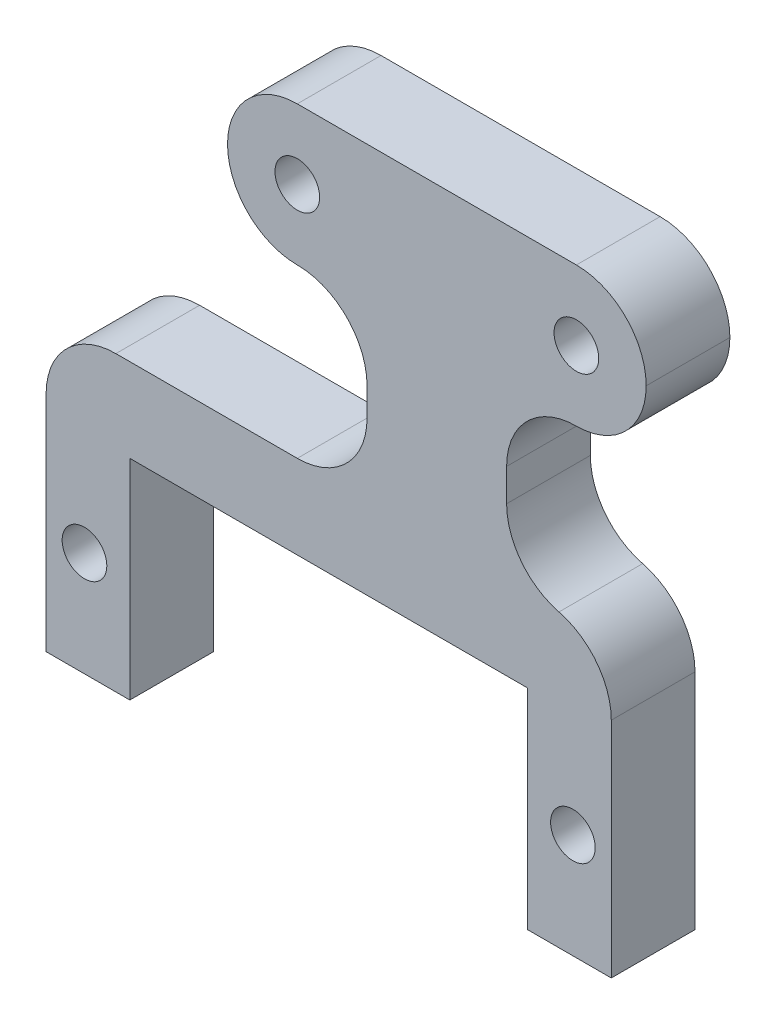
SolidWorks part; units mm, degrees
ref_plane "Plan de face" through (0, 0, 0) normal (0, 0, 1) x (1, 0, 0)
ref_plane "Plan de dessus" through (0, 0, 0) normal (0, 1, 0) x (1, 0, 0)
ref_plane "Plan de droite" through (0, 0, 0) normal (1, 0, 0) x (0, 0, -1)
sketch "Esquisse1" plane through (0, 0, 0) normal (0, 0, 1) x (1, 0, 0)
  line L0 (12.75, 18) -> (22.75, 18)
  line L1 (-14.25, 0) -> (14.25, 0)
  line L2 (-20.25, 0) -> (-20.25, 6)
  line L3 (-20.25, 6) -> (2.75, 6)
  line L4 (20.25, -0.6948) -> (20.25, 6)
  line L5 (12.75, 6) -> (20.25, 6)
  line L6 (20.25, -0.6948) -> (20.25, -15)
  line L7 (20.25, -15) -> (14.25, -15)
  line L8 (14.25, 0) -> (14.25, -15)
  line L10 (-20.25, 0) -> (-20.25, -15)
  line L11 (-20.25, -15) -> (-14.25, -15)
  line L12 (-14.25, 0) -> (-14.25, -15)
  line L14 (12.75, 6) -> (12.75, 18)
  line L16 (2.75, 6) -> (2.75, 18)
  line L17 (-7.25, 18) -> (2.75, 18)
  line L18 (-7.25, 18) -> (-7.25, 28)
  line L19 (-7.25, 28) -> (22.75, 28)
  line L20 (22.75, 18) -> (22.75, 28)
  dimension "D1" = 28.5
  dimension "D2" = 6
  dimension "D3" = 6
  dimension "D4" = 6
  dimension "D5" = 10
  dimension "D6" = 1.5
  dimension "D7" = 10
  dimension "D8" = 30
  dimension "D9" = 10
  dimension "D10" = 14.25
  dimension "D11" = 6
  dimension "D12" = 15
  dimension "D13" = 15
  dimension "D14" = 0
  dimension "D15" = 12
extrude "Boss.-Extru.1" add sketch "Esquisse1" along normal blind 6
sketch "Esquisse2" plane through (0, 0, 6) normal (0, 0, 1) x (1, 0, 0)
  line L0 (-14.25, 0) -> (14.25, 0) construction
  circle A0 centre (-17.5, -7.5) radius 1.6
  circle A1 centre (17.5, -7.5) radius 1.6
  point P6 (0, 0)
  dimension "D1" = 3.2
  dimension "D2" = 3.2
  dimension "D3" = 7.5
  dimension "D4" = 7.5
  dimension "D5" = 35
  dimension "D6" = 17.5
extrude "Enlèv. mat.-Extru.1" cut sketch "Esquisse2" against normal blind 10
sketch "Esquisse4" plane through (0, 0, 0) normal (0, 0, -1) x (-1, 0, 0)
  line L0 (-22.75, 18) -> (-22.75, 28) construction
  line L1 (-22.75, 28) -> (7.25, 28) construction
  line L2 (7.25, 28) -> (7.25, 18) construction
  circle A0 centre (-17.75, 23) radius 1.6
  circle A1 centre (2.25, 23) radius 1.6
  dimension "D1" = 3.2
  dimension "D2" = 3.2
  dimension "D3" = 5
  dimension "D4" = 5
  dimension "D5" = 5
  dimension "D6" = 5
extrude "Enlèv. mat.-Extru.2" cut sketch "Esquisse4" against normal through all
chamfer "Chanfrein1" distance 2.1 angle 45 2 edges at (-3.85, 23, 0) (16.15, 23, 0)
fillet "Congé1" radius 5 9 edges at (2.75, 6, 3) (-20.25, 6, 3) (20.25, 6, 3) (-7.25, 28, 3) (-7.25, 18, 3) (2.75, 18, 3) (12.75, 18, 3) (22.75, 18, 3) (22.75, 28, 3)
fillet "Congé2" radius 5 1 edges at (12.75, 6, 3)
